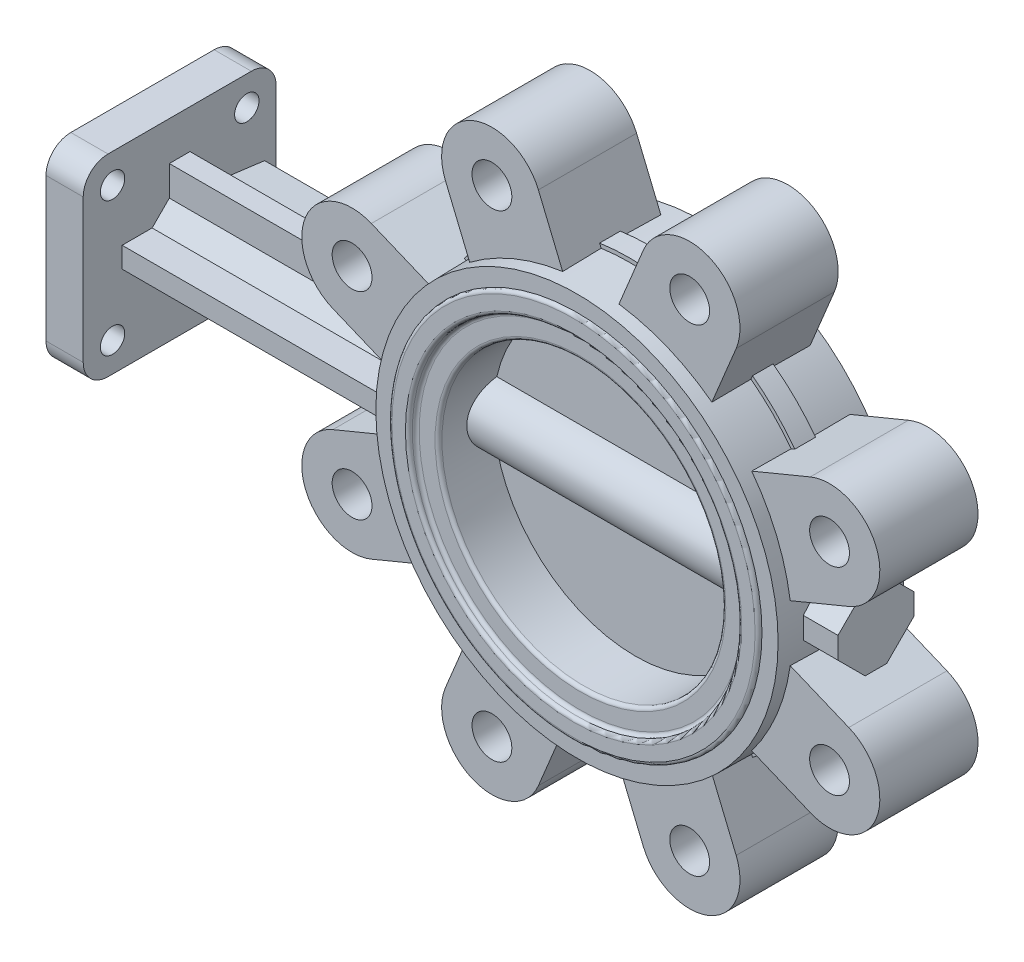
SolidWorks part; units mm, degrees
material "A36"
ref_plane "Front Plane" through (0, 0, 0) normal (0, 0, 1) x (1, 0, 0)
ref_plane "Top Plane" through (0, 0, 0) normal (0, 1, 0) x (1, 0, 0)
ref_plane "Right Plane" through (0, 0, 0) normal (1, 0, 0) x (0, 0, -1)
sketch "Sketch1" plane through (0, 0, 0) normal (0, 0, 1) x (1, 0, 0)
  circle A0 centre (0, 0) radius 74.549
  dimension "D1" = 149.098
extrude "Boss-Extrude1" add sketch "Sketch1" along normal mid plane 46.3931 draft 1
sketch "Sketch2" plane through (0, 0, 23.1965) normal (0, 0, 1) x (1, 0, 0)
  circle A0 centre (0, 0) radius 68.199
  dimension "D1" = 136.398
extrude "Boss-Extrude2" add sketch "Sketch2" along normal blind 1.27
sketch "Sketch3" plane through (0, 0, -23.1965) normal (0, 0, -1) x (-1, 0, 0)
  circle A0 centre (0, 0) radius 68.199
  dimension "D1" = 136.398
extrude "Boss-Extrude3" add sketch "Sketch3" along normal blind 1.27
sketch "Sketch4" plane through (0, 0, -24.4666) normal (0, 0, -1) x (-1, 0, 0)
  circle A0 centre (0, 0) radius 60.706
  dimension "D1" = 121.412
extrude "Cut-Extrude1" cut sketch "Sketch4" against normal blind 2.54
sketch "Sketch5" plane through (0, 0, 24.4666) normal (0, 0, 1) x (1, 0, 0)
  circle A0 centre (0, 0) radius 60.706
  dimension "D1" = 121.412
extrude "Cut-Extrude2" cut sketch "Sketch5" against normal blind 2.54
sketch "Sketch6" plane through (0, 0, 21.9265) normal (0, 0, 1) x (1, 0, 0)
  circle A0 centre (0, 0) radius 52.324
  dimension "D1" = 104.648
extrude "Cut-Extrude3" cut sketch "Sketch6" against normal through all
sketch "Sketch7" plane through (0, 0, 0) normal (0, 1, 0) x (1, 0, 0)
  line L1 (-75.9221, 3.81) -> (-69.5721, 3.81)
  line L2 (-75.9221, 3.81) -> (-75.9221, -3.81)
  line L3 (-75.9221, -3.81) -> (-69.5721, -3.81)
  line L4 (-69.5721, 3.81) -> (-69.5721, -3.81)
  line L5 (-75.9221, 0) -> (-74.549, 0) construction
  line L7 (0, 0) -> (0, 23.1965) construction
  line L8 (74.1441, 23.1965) -> (-74.1441, 23.1965) construction
  dimension "D1" = 7.62
  dimension "D2" = 1.778
  dimension "D3" = 6.35
revolve "Revolve1" add sketch "Sketch7" angle 360 about L7
ref_plane "Plane1" through (68.199, 0, 0) normal (1, 0, 0) x (0, 0, -1)
sketch "Sketch8" plane through (68.199, 0, 0) normal (1, 0, 0) x (0, 0, -1)
  line L1 (-13.97, 13.97) -> (13.97, 13.97)
  line L2 (-13.97, 13.97) -> (-13.97, -13.97)
  line L3 (-13.97, -13.97) -> (13.97, -13.97)
  line L4 (13.97, 13.97) -> (13.97, -13.97)
  line L5 (-13.97, 13.97) -> (13.97, -13.97) construction
  line L6 (-13.97, -13.97) -> (13.97, 13.97) construction
  point P0 (0, 0)
  dimension "D1" = 27.94
extrude "Boss-Extrude4" add sketch "Sketch8" along normal blind 18.796
chamfer "Chamfer1" distance 10 angle 45 4 edges at (79.9875, 13.97, -13.97) (79.9875, -13.97, -13.97) (79.9875, -13.97, 13.97) (79.9875, 13.97, 13.97)
ref_plane "Plane2" through (-75.9221, 0, 0) normal (-1, 0, 0) x (0, 0, 1)
sketch "Sketch9" plane through (-75.9221, 0, 0) normal (-1, 0, 0) x (0, 0, 1)
  line L0 (-3.81, 75.9221) -> (-3.81, -75.9221) construction
  line L1 (-21.209, 3.81) -> (-3.81, 3.81)
  line L2 (-21.209, 3.81) -> (-21.209, -3.81)
  line L3 (-21.209, -3.81) -> (-3.81, -3.81)
  line L4 (21.209, 3.81) -> (21.209, -3.81)
  line L5 (-21.209, 3.81) -> (21.209, -3.81) construction
  line L6 (-21.209, -3.81) -> (21.209, 3.81) construction
  line L7 (-3.81, -21.209) -> (3.81, -21.209)
  line L8 (-3.81, -21.209) -> (-3.81, -3.81)
  line L9 (-3.81, 21.209) -> (3.81, 21.209)
  line L10 (3.81, -21.209) -> (3.81, -3.81)
  line L11 (-3.81, -21.209) -> (3.81, 21.209) construction
  line L12 (-3.81, 21.209) -> (3.81, -21.209) construction
  line L13 (3.81, 3.81) -> (21.209, 3.81)
  line L14 (-3.81, 3.81) -> (-3.81, 21.209)
  line L15 (3.81, 3.81) -> (3.81, 21.209)
  line L19 (3.81, -3.81) -> (21.209, -3.81)
  point P0 (0, 0)
  point P5 (0, 0)
  dimension "D1" = 42.418
  dimension "D2" = 42.418
extrude "Boss-Extrude5" add sketch "Sketch9" along normal blind 93.726 and the other way blind 12.7
sketch "Sketch11" plane through (-169.6481, 0, 0) normal (-1, 0, 0) x (0, 0, 1)
  line L1 (35.56, 35.56) -> (-35.56, 35.56)
  line L2 (35.56, 35.56) -> (35.56, -35.56)
  line L3 (35.56, -35.56) -> (-35.56, -35.56)
  line L4 (-35.56, 35.56) -> (-35.56, -35.56)
  line L5 (35.56, 35.56) -> (-35.56, -35.56) construction
  line L6 (35.56, -35.56) -> (-35.56, 35.56) construction
  point P0 (0, 0)
  dimension "D1" = 71.12
extrude "Boss-Extrude7" add sketch "Sketch11" along normal blind 13.716
chamfer "Chamfer2" distance 6.35 angle 45 4 edges at (-122.0165, 3.81, 3.81) (-122.0165, -3.81, 3.81) (-122.0165, -3.81, -3.81) (-122.0165, 3.81, -3.81)
fillet "Fillet1" radius 9.144 4 edges at (-176.5061, 35.56, -35.56) (-176.5061, 35.56, 35.56) (-176.5061, -35.56, -35.56) (-176.5061, -35.56, 35.56)
sketch "Sketch12" plane through (0, 0, -3.81) normal (0, 0, -1) x (-1, 0, 0)
  line L0 (169.6481, 26.416) -> (169.6481, -26.416) construction
  line L1 (160.7581, 15.875) -> (103.6081, 15.875)
  line L2 (160.7581, 15.875) -> (160.7581, -15.875)
  line L3 (160.7581, -15.875) -> (103.6081, -15.875)
  line L4 (103.6081, 15.875) -> (103.6081, -15.875)
  line L5 (160.7581, 15.875) -> (103.6081, -15.875) construction
  line L6 (160.7581, -15.875) -> (103.6081, 15.875) construction
  line L7 (132.1831, 0) -> (0, 0) construction
  point P0 (132.1831, 0)
  dimension "D1" = 57.15
  dimension "D2" = 31.75
  dimension "D3" = 8.89
extrude "Boss-Extrude8" add sketch "Sketch12" along normal up to surface (17.399 mm away) draft 4
fillet "Fillet2" radius 1.27 7 edges at (60.706, 0, 21.9265) (52.324, 0, 21.9265) (-52.324, 0, -21.9265) (68.199, 0, 24.4666) (60.706, 0, 24.4666) (-68.199, 0, -24.4666) (-60.706, 0, -24.4666)
sketch "Sketch14" plane through (-183.3641, 0, 0) normal (-1, 0, 0) x (0, 0, 1)
  circle A0 centre (0, 0) radius 9.525
  dimension "D1" = 19.05
extrude "Cut-Extrude5" cut sketch "Sketch14" against normal blind 7.62
hole_wizard "M8 Clearance Hole1" positions "Sketch16" profile "Sketch17" hole size "M8" standard "ANSI Metric"
sketch "Sketch16" plane through (-183.3641, 0, 0) normal (-1, 0, 0) x (0, 0, 1)
  line L1 (-24.7487, 24.7487) -> (24.7487, 24.7487)
  line L2 (-24.7487, 24.7487) -> (-24.7487, -24.7487)
  line L3 (-24.7487, -24.7487) -> (24.7487, -24.7487)
  line L4 (24.7487, 24.7487) -> (24.7487, -24.7487)
  line L5 (0, 0) -> (0, 24.7487)
  line L6 (0, 0) -> (0, -24.7487)
  point P0 (-24.7487, 24.7487)
  point P2 (24.7487, 24.7487)
  point P4 (24.7487, -24.7487)
  point P6 (-24.7487, -24.7487)
  dimension "D1" = 70
sketch "Sketch17" plane through (-183.3641, 24.7487, -24.7487) normal (0, 1, 0) x (0, 0, 1)
  line L0 (0, 0) -> (0, 13.716)
  line L1 (0, 13.716) -> (4.5, 13.716)
  line L2 (4.5, 13.716) -> (4.5, 0)
  line L5 (4.5, 0) -> (0, 0)
  line L11 (0, -6.35) -> (0, 107.95) construction
  dimension "Thru Hole Dia." = 9
  dimension "Thru Hole Depth" = 13.716
sketch "Sketch18" plane through (86.995, 0, 0) normal (1, 0, 0) x (0, 0, -1)
  circle A0 centre (0, 0) radius 11.5
  dimension "D1" = 23
extrude "Boss-Extrude9" add sketch "Sketch18" against normal blind 142.24
sketch "Sketch19" plane through (-175.7441, 0, 0) normal (-1, 0, 0) x (0, 0, 1)
  circle A0 centre (0, 0) radius 7
  dimension "D1" = 14
extrude "Boss-Extrude10" add sketch "Sketch19" along normal offset from surface (6.62 mm away) 1 up to face at (-183.3641, 0, 9.525)
sketch "Sketch20" plane through (-182.3641, 0, 0) normal (-1, 0, 0) x (0, 0, 1)
  line L0 (0, 7.7782) -> (-7.7782, 0)
  line L5 (0, -7.7782) -> (7.7782, 0)
  line L6 (7.7782, 0) -> (0, 7.7782)
  line L7 (-7.7782, 0) -> (0, -7.7782)
  line L8 (-7.7782, 0) -> (7.7782, 0) construction
  line L9 (0, 7.7782) -> (0, -7.7782) construction
  point P4 (0, 0)
  dimension "D1" = 11
  dimension "D2" = 90
extrude "Boss-Extrude11" add sketch "Sketch20" along normal blind 19
chamfer "Chamfer3" distance 1.5 angle 45 4 edges at (-191.8641, -7.7782, 0) (-191.8641, 0, 7.7782) (-191.8641, 7.7782, 0) (-191.8641, 0, -7.7782)
sketch "Sketch21" plane through (0, 0, 0) normal (0, 0, 1) x (1, 0, 0)
  circle A0 centre (0, 0) radius 52.324
  circle A1 centre (0, 0) radius 52.324 construction
extrude "Boss-Extrude12" add sketch "Sketch21" along normal mid plane 3.33
sketch "Sketch22" plane through (0, 0, 0) normal (0, 0, 1) x (1, 0, 0)
  line L1 (0, 0) -> (-87.9995, 36.4506) construction
  line L2 (-74.1441, 0) -> (-183.3641, 0) construction
  line L4 (0, 0) -> (-48.4526, 0) construction
  line L5 (-183.3641, -26.416) -> (-183.3641, 26.416) construction
  line L7 (-80.9038, 53.5812) -> (-59.2279, 44.6027)
  line L8 (-95.0952, 19.32) -> (-73.4193, 10.3416)
  circle A4 centre (0, 0) radius 74.1441 construction
  arc A8 (-80.9038, 53.5812) -> (-95.0952, 19.32) centre (-87.9995, 36.4506) ccw
  arc A9 (-59.2279, 44.6027) -> (-73.4193, 10.3416) centre (0, 0) ccw
  dimension "D2" = 18.542
  dimension "D1" = 22.5
  dimension "D5" = 95.25
extrude "Boss-Extrude13" add sketch "Sketch22" along normal mid plane 36.195
pattern_circular "CirPattern1" count 8 over 360 about axis through (0, 0, 0) along (0, 0, 1) of "Boss-Extrude13"
hole_wizard "5/8-18 Tapped Hole1" positions "Sketch23" profile "Sketch24" tap size "5/8-18" standard "ANSI Inch" end condition through all
sketch "Sketch23" plane through (0, 0, 18.0975) normal (0, 0, 1) x (1, 0, 0)
  point P0 (-87.9995, -36.4506)
  point P3 (-87.9995, 36.4506)
  point P6 (36.4506, -87.9995)
  point P9 (-36.4506, -87.9995)
  point P12 (87.9995, -36.4506)
  point P15 (87.9995, 36.4506)
  point P18 (36.4506, 87.9995)
  point P21 (-36.4506, 87.9995)
sketch "Sketch24" plane through (-87.9995, -36.4506, 18.0975) normal (1, 0, 0) x (0, -1, 0)
  line L0 (0, 0) -> (0, 53.6575)
  line L1 (0, 53.6575) -> (7.3419, 53.6575)
  line L2 (7.3419, 53.6575) -> (7.3419, 0)
  line L5 (7.3419, 0) -> (0, 0)
  line L11 (0, -6.35) -> (0, 107.95) construction
  dimension "Thru Tap Drill Dia." = 14.6837
  dimension "Thru Tap Drill Depth" = 53.6575
cosmetic thread "Hole Thread1" parameters "D2"=15.875
cosmetic thread "Hole Thread4" parameters "D2"=15.875
cosmetic thread "Hole Thread5" parameters "D2"=15.875
cosmetic thread "Hole Thread6" parameters "D2"=15.875
cosmetic thread "Hole Thread7" parameters "D2"=15.875
cosmetic thread "Hole Thread8" parameters "D2"=15.875
cosmetic thread "Hole Thread9" parameters "D2"=15.875
cosmetic thread "Hole Thread10" parameters "D2"=15.875
